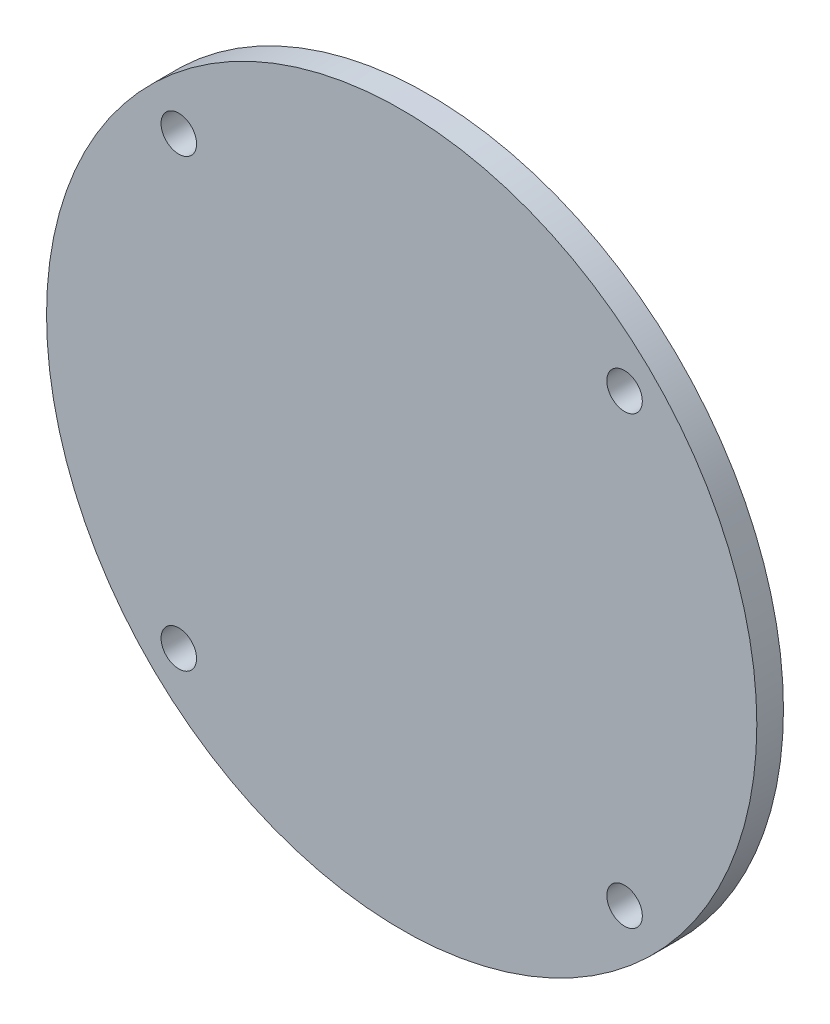
SolidWorks part; units mm, degrees
ref_plane "前视基准面" through (0, 0, 0) normal (0, 0, 1) x (1, 0, 0)
ref_plane "上视基准面" through (0, 0, 0) normal (0, 1, 0) x (1, 0, 0)
ref_plane "右视基准面" through (0, 0, 0) normal (1, 0, 0) x (0, 0, -1)
sketch "草图1" plane through (0, 0, 0) normal (0, 0, 1) x (1, 0, 0)
  line L1 (-25.1023, -25.1023) -> (25.1023, -25.1023)
  line L2 (-25.1023, -25.1023) -> (-25.1023, 25.1023)
  line L3 (-25.1023, 25.1023) -> (25.1023, 25.1023)
  line L4 (25.1023, -25.1023) -> (25.1023, 25.1023)
  line L5 (-25.1023, -25.1023) -> (25.1023, 25.1023) construction
  line L6 (-25.1023, 25.1023) -> (25.1023, -25.1023) construction
  circle A0 centre (0, 0) radius 40
  circle A1 centre (-25.1023, 25.1023) radius 2
  circle A2 centre (25.1023, 25.1023) radius 2
  circle A3 centre (25.1023, -25.1023) radius 2
  circle A4 centre (-25.1023, -25.1023) radius 2
  dimension "D2" = 80
  dimension "D4" = 4
  dimension "D5" = 4
  dimension "D6" = 4
  dimension "D7" = 4
  dimension "D1" = 71
extrude "凸台-拉伸1" add sketch "草图1" along normal blind 3 contours A0 A4 L2 A1 L3 A2 L4 A3 L1 | A4 L1 A3 L4 A2 L3 A1 L2 region at (0, 0, 0) region at (-38.8686, 0, 0)
